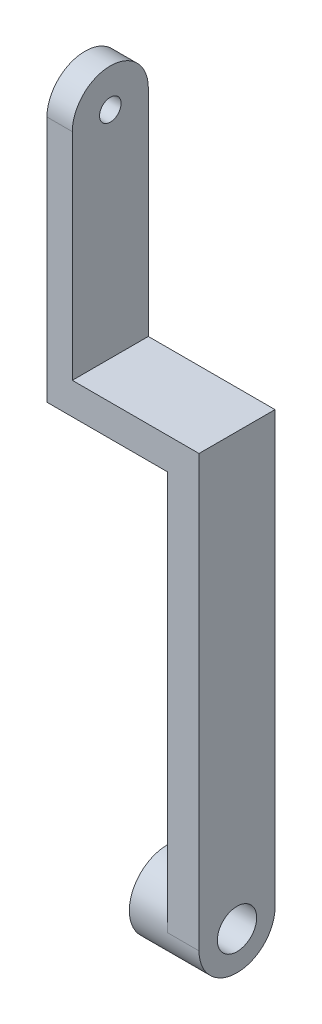
SolidWorks part; units mm, degrees
ref_plane "前视基准面" through (0, 0, 0) normal (0, 0, 1) x (1, 0, 0)
ref_plane "上视基准面" through (0, 0, 0) normal (0, 1, 0) x (1, 0, 0)
ref_plane "右视基准面" through (0, 0, 0) normal (1, 0, 0) x (0, 0, -1)
other "Configuration Table"
sketch "草图1" plane through (0, 0, 0) normal (0, 0, 1) x (1, 0, 0)
  line L0 (-2, -2.5) -> (7.5, -2.5)
  line L2 (0, 0) -> (0, 20)
  line L3 (0, 20) -> (-2, 20)
  line L4 (-2, 8.2736) -> (-2, 20)
  line L5 (0, 0) -> (10, 0)
  line L6 (-2, 8.2736) -> (-2, -2.5)
  line L7 (7.5, -37) -> (10, -37)
  line L8 (10, 0) -> (10, -37)
  line L9 (7.5, -2.5) -> (7.5, -37)
  dimension "D1" = 37
  dimension "D2" = 2
  dimension "D3" = 20
  dimension "D4" = 2.5
  dimension "D5" = 2.5
  dimension "D6" = 10
extrude "凸台-拉伸1" add sketch "草图1" along normal blind 6
fillet "圆角3" 2 edges at (-1, 20, 0) (-1, 20, 6) type full round first side face at (3.875, -4.875, 0) second side face at (3.875, -4.875, 6) middle face at (-1, 20, 3)
fillet "圆角4" 2 edges at (8.75, -37, 0) (8.75, -37, 6) type full round first side face at (3.875, -5.625, 0) second side face at (3.875, -5.625, 6) middle face at (8.75, -37, 3)
sketch "草图2" plane through (-2, 0, 0) normal (-1, 0, 0) x (0, 0, 1)
  circle A0 centre (3, 17) radius 0.85
  circle A1 centre (3, -34) radius 1.55
  arc A2 (6, 17) -> (0, 17) centre (3, 17) ccw construction
  arc A3 (0, -34) -> (6, -34) centre (3, -34) ccw construction
  dimension "D1" = 1.7
  dimension "D2" = 3.1
extrude "切除-拉伸1" cut sketch "草图2" against normal through all contours A0 | A1
sketch "草图3" plane through (7.5, 0, 0) normal (-1, 0, 0) x (0, 0, 1)
  circle A0 centre (3, -34) radius 3
  circle A1 centre (3, -34) radius 1.55
  dimension "D1" = 6
extrude "凸台-拉伸2" add sketch "草图3" along normal blind 3
